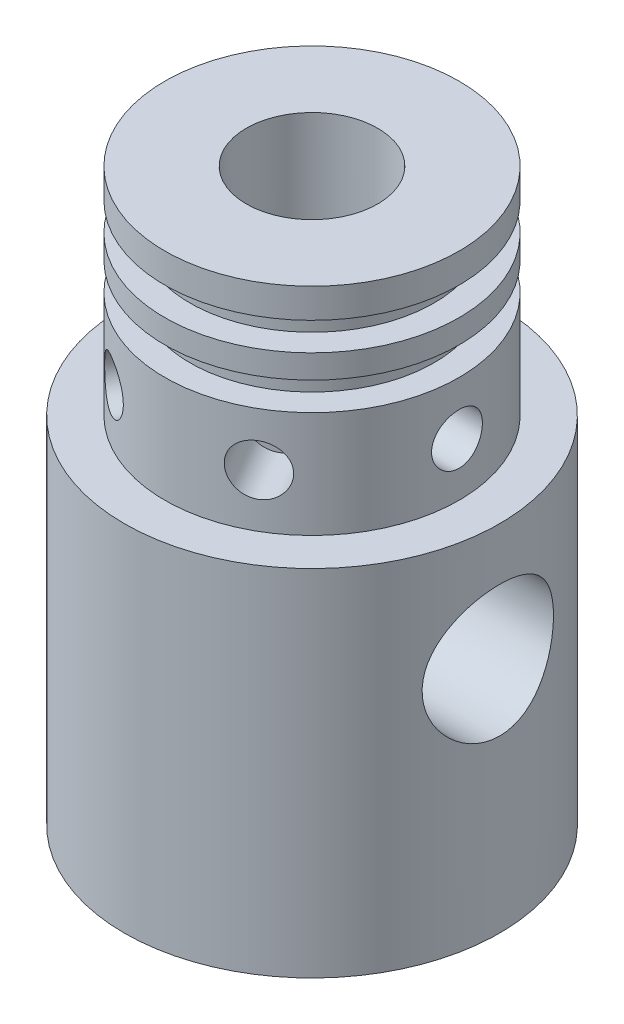
SolidWorks part; units mm, degrees
ref_plane "Front Plane" through (0, 0, 0) normal (0, 0, 1) x (1, 0, 0)
ref_plane "Top Plane" through (0, 0, 0) normal (0, 1, 0) x (1, 0, 0)
ref_plane "Right Plane" through (0, 0, 0) normal (1, 0, 0) x (0, 0, -1)
sketch "Sketch1" plane through (0, 0, 0) normal (0, 0, 1) x (1, 0, 0)
  line L0 (0, -19.1312) -> (15.875, -19.1312)
  line L1 (15.875, -19.1312) -> (15.875, 0.8688)
  line L2 (15.875, 0.8688) -> (12.45, 0.8688)
  line L3 (12.45, 0.8688) -> (12.45, 9.8688)
  line L4 (12.45, 9.8688) -> (10.3187, 9.8688)
  line L5 (10.3187, 9.8688) -> (10.3187, 12.25)
  line L6 (10.3187, 12.25) -> (12.45, 12.25)
  line L7 (12.45, 12.25) -> (12.45, 14.25)
  line L8 (12.45, 14.25) -> (10.3188, 14.25)
  line L9 (10.3188, 14.25) -> (10.3188, 16.6313)
  line L10 (10.3188, 16.6313) -> (12.45, 16.6313)
  line L11 (12.45, 16.6313) -> (12.45, 19.1313)
  line L12 (12.45, 19.1313) -> (0, 19.1312)
  line L13 (0, 19.1312) -> (0, -19.1312)
  line L14 (0, -8.095) -> (0, 15.2312) construction
  line L15 (12.7, 19.4771) -> (12.7, -5.4015) construction
  line L16 (10.3187, 11.0594) -> (12.7, 11.0594) construction
  point P18 (0, 0)
  dimension "D1" = 12.7
  dimension "D2" = 0.5
  dimension "D3" = 31.75
  dimension "D4" = 20
  dimension "D5" = 20.6375
  dimension "D6" = 2
  dimension "D7" = 2.5
  dimension "D8" = 9
revolve "Revolve1" add sketch "Sketch1" angle 360 about L14
sketch "Sketch2" plane through (0, 0, 0) normal (1, 0, 0) x (0, 0, -1)
  line L0 (0, 0.8688) -> (0, -19.1312) construction
  line L1 (15.875, 0.8688) -> (-15.875, 0.8688) construction
  line L2 (-15.875, -19.1312) -> (15.875, -19.1312) construction
  circle A0 centre (0, -9.1312) radius 5.5562
  dimension "D1" = 11.1125
extrude "Cut-Extrude1" cut sketch "Sketch2" against normal through all both and the other way through all
sketch "Sketch3" plane through (0, 19.1313, 0) normal (0, 1, 0) x (1, 0, 0)
  line L0 (-14.8709, 5.5563) -> (14.8709, 5.5563) construction
  circle A0 centre (0, 0) radius 5.5563
  arc A1 (14.8709, -5.5562) -> (14.8709, 5.5563) centre (0, 0) ccw construction
  arc A2 (14.8709, -5.5562) -> (14.8709, 5.5563) centre (0, 0) ccw construction
  arc A3 (-14.8709, 5.5563) -> (-14.8709, -5.5562) centre (0, 0) ccw construction
  arc A4 (-14.8709, 5.5563) -> (-14.8709, -5.5562) centre (0, 0) ccw construction
extrude "Cut-Extrude2" cut sketch "Sketch3" against normal up to next
ref_plane "Plane1" through (12.45, 0, 0) normal (1, 0, 0) x (0, 0, -1)
sketch "Sketch4" plane through (12.45, 0, 0) normal (1, 0, 0) x (0, 0, -1)
  line L0 (0, 0.8688) -> (0, 9.8688) construction
  line L1 (15.875, 0.8688) -> (-15.875, 0.8688) construction
  line L2 (12.45, 9.8688) -> (-12.45, 9.8688) construction
  circle A0 centre (0, 5.3688) radius 2.15
  dimension "D1" = 4.3
extrude "Cut-Extrude3" cut sketch "Sketch4" against normal blind 5
pattern_circular "CirPattern1" count 6 over 360 about axis through (0, -8.095, 0) along (0, -1, 0) of "Cut-Extrude3"
sketch "Sketch5" plane through (0, -19.1312, 0) normal (0, -1, 0) x (1, 0, 0)
  circle A1 centre (0, 0) radius 15.875
  circle A2 centre (0, 0) radius 15.875
  dimension "D1" = 0
extrude "Boss-Extrude1" add sketch "Sketch5" along normal blind 10
